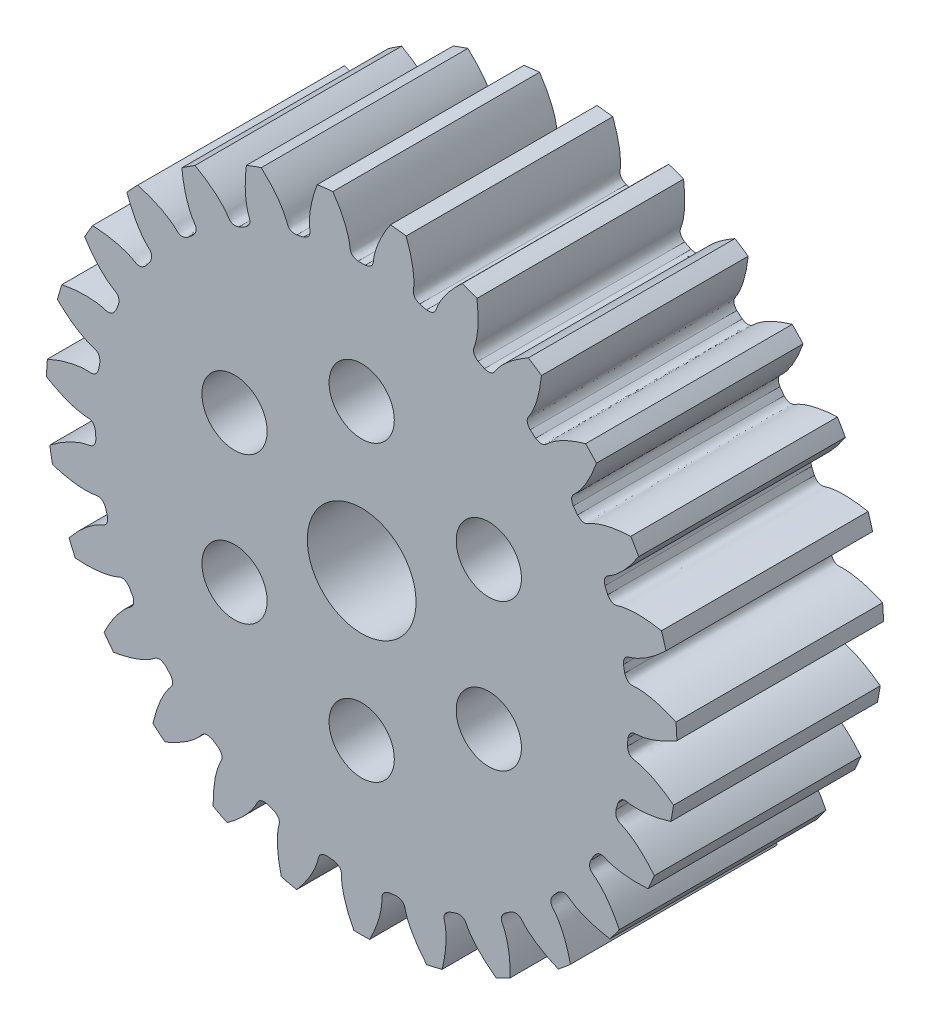
SolidWorks part; units mm, degrees
ref_plane "前视基准面" through (0, 0, 0) normal (0, 0, 1) x (1, 0, 0)
ref_plane "上视基准面" through (0, 0, 0) normal (0, 1, 0) x (1, 0, 0)
ref_plane "右视基准面" through (0, 0, 0) normal (1, 0, 0) x (0, 0, -1)
other "Configuration Table"
sketch "草图1" plane through (0, 0, 0) normal (0, 0, 1) x (1, 0, 0)
  circle A0 centre (0, 0) radius 29
extrude "凸台-拉伸1" add sketch "草图1" against normal mid plane 19
ref_axis "基准轴1" through (0, 0, 9.5) along (0, 0, -1)
sketch "草图2" plane through (0, 0, 0) normal (0, 0, 1) x (1, 0, 0)
  line L0 (0, 0) -> (0, 29) construction
  circle A0 centre (0, 0) radius 29 construction
  arc A1 (0.3239, 24.4979) -> (-0.3239, 24.4979) centre (0, 0) ccw
  arc A2 (6.4196, 32.8422) -> (-6.4196, 32.8422) centre (0, 0) ccw
  spline S0 degree 3 poles (0.3239, 24.4979) (1.1069, 24.624) (1.0502, 25.0768) (1.1212, 25.5325) (1.1326, 25.5975) (1.1473, 25.6722) (1.1656, 25.7565) (1.188, 25.8503) (1.2147, 25.9534) (1.2463, 26.0658) (1.283, 26.1872) (1.3253, 26.3175) (1.3735, 26.4566) (1.428, 26.6042) (1.4891, 26.7601) (1.5572, 26.9241) (1.6326, 27.096) (1.7158, 27.2756) (1.8069, 27.4627) (1.9065, 27.6569) (2.0146, 27.858) (2.1318, 28.0657) (2.2583, 28.2798) (2.3943, 28.5) (2.5402, 28.7259) (2.6963, 28.9573) (2.8629, 29.1938) (3.0401, 29.4351) (3.2283, 29.6809) (3.4277, 29.9308) (3.6385, 30.1844) (3.861, 30.4415) (4.0954, 30.7016) (4.3419, 30.9644) (4.6007, 31.2294) (4.872, 31.4964) (5.1559, 31.7648) (5.4527, 32.0344) (5.8708, 32.3991) (6.1965, 32.6663) (6.4196, 32.8422) knots 0 0 0 0 0.119962 0.125269 0.131541 0.138778 0.14698 0.156147 0.166279 0.177376 0.189438 0.202465 0.216457 0.231414 0.247336 0.264222 0.282074 0.300891 0.320672 0.341419 0.36313 0.385807 0.409448 0.434054 0.459626 0.486162 0.513663 0.542129 0.57156 0.601956 0.633317 0.665643 0.698934 0.73319 0.768411 0.804597 0.841747 0.879863 0.918944 1 1 1 1
  spline S1 degree 3 poles (-0.3239, 24.4979) (-1.1069, 24.624) (-1.0502, 25.0768) (-1.1212, 25.5325) (-1.1326, 25.5975) (-1.1473, 25.6722) (-1.1656, 25.7565) (-1.188, 25.8503) (-1.2147, 25.9534) (-1.2463, 26.0658) (-1.283, 26.1872) (-1.3253, 26.3175) (-1.3735, 26.4566) (-1.428, 26.6042) (-1.4891, 26.7601) (-1.5572, 26.9241) (-1.6326, 27.096) (-1.7158, 27.2756) (-1.8069, 27.4627) (-1.9065, 27.6569) (-2.0146, 27.858) (-2.1318, 28.0657) (-2.2583, 28.2798) (-2.3943, 28.5) (-2.5402, 28.7259) (-2.6963, 28.9573) (-2.8629, 29.1938) (-3.0401, 29.4351) (-3.2283, 29.6809) (-3.4277, 29.9308) (-3.6385, 30.1844) (-3.861, 30.4415) (-4.0954, 30.7016) (-4.3419, 30.9644) (-4.6007, 31.2294) (-4.872, 31.4964) (-5.1559, 31.7648) (-5.4527, 32.0344) (-5.8708, 32.3991) (-6.1965, 32.6663) (-6.4196, 32.8422) knots 0 0 0 0 0.119962 0.125269 0.131541 0.138778 0.14698 0.156147 0.166279 0.177376 0.189438 0.202465 0.216457 0.231414 0.247336 0.264222 0.282074 0.300891 0.320672 0.341419 0.36313 0.385807 0.409448 0.434054 0.459626 0.486162 0.513663 0.542129 0.57156 0.601956 0.633317 0.665643 0.698934 0.73319 0.768411 0.804597 0.841747 0.879863 0.918944 1 1 1 1
extrude "切除-拉伸1" cut sketch "草图2" against normal through all both and the other way through all
pattern_circular "阵列(圆周)1" count 27 over 360 about axis through (0, 0, 9.5) along (0, 0, -1) of "切除-拉伸1"
sketch "草图3" plane through (0, 0, 0) normal (0, 0, 1) x (1, 0, 0)
  circle A0 centre (0, 0) radius 27 construction
  dimension "Dn" = 54
sketch "草图8" plane through (0, 0, -9.5) normal (0, 0, -1) x (-1, 0, 0)
  circle A0 centre (0, 0) radius 17.5
  dimension "D1" = 35
extrude "凸台-拉伸2" add sketch "草图8" along normal blind 4.5
sketch "草图4" plane through (0, 0, 9.5) normal (0, 0, 1) x (1, 0, 0)
  circle A0 centre (0, 0) radius 13.5 construction
  circle A1 centre (0, 13.5) radius 1.6
  circle A2 centre (11.6913, 6.75) radius 1.6
  circle A3 centre (11.6913, -6.75) radius 1.6
  circle A4 centre (0, -13.5) radius 1.6
  circle A5 centre (-11.6913, -6.75) radius 1.6
  circle A6 centre (-11.6913, 6.75) radius 1.6
  dimension "D1" = 27
  dimension "D2" = 3.2
  dimension "D3" = 6
extrude "切除-拉伸2" cut sketch "草图4" against normal through all
sketch "草图5" plane through (0, 0, 9.5) normal (0, 0, 1) x (1, 0, 0)
  circle A0 centre (0, 13.5) radius 3
  circle A1 centre (11.6913, 6.75) radius 3
  circle A2 centre (11.6913, -6.75) radius 3
  circle A3 centre (0, -13.5) radius 3
  circle A4 centre (-11.6913, -6.75) radius 3
  circle A5 centre (-11.6913, 6.75) radius 3
  dimension "D1" = 6
extrude "切除-拉伸3" cut sketch "草图5" against normal offset from surface (20.5 mm away) 3 up to face at (1.6, 13.5, -14)
sketch "草图6" plane through (0, 0, 9.5) normal (0, 0, 1) x (1, 0, 0)
  circle A0 centre (0, 0) radius 5
  dimension "D1" = 10
extrude "切除-拉伸4" cut sketch "草图6" against normal through all
